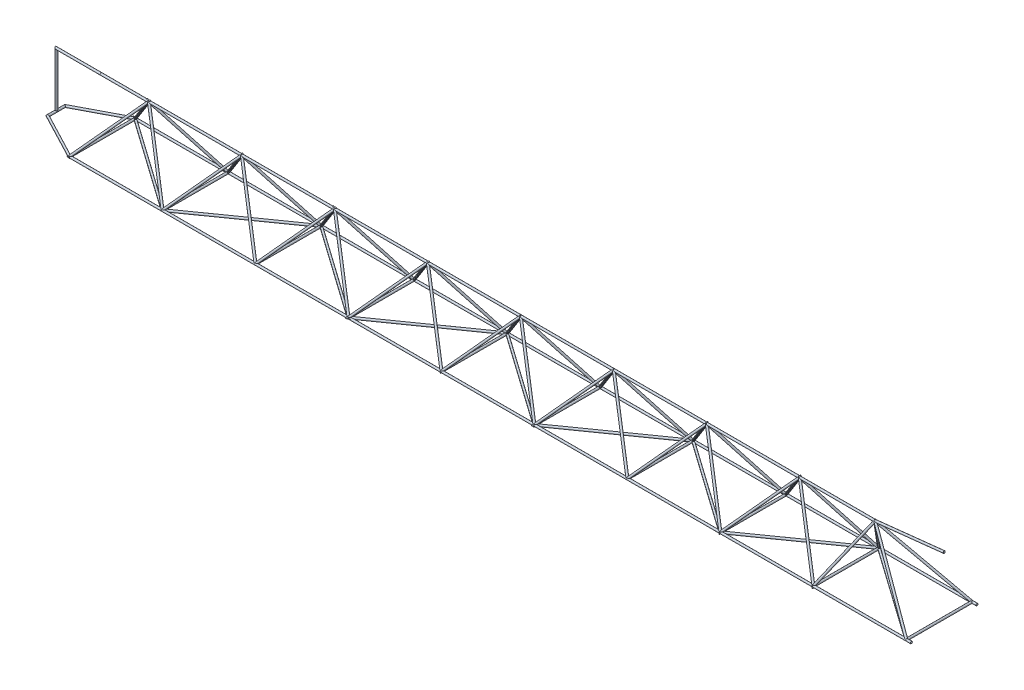
SolidWorks part; units mm, degrees
material "AVG Gam ARM"
ref_plane "Front Plane" through (0, 0, 0) normal (0, 0, 1) x (1, 0, 0)
ref_plane "Top Plane" through (0, 0, 0) normal (0, 1, 0) x (1, 0, 0)
ref_plane "Right Plane" through (0, 0, 0) normal (1, 0, 0) x (0, 0, -1)
sketch3d "3DSketch1"
  line L0 (-4292.6, 0, 0) -> (-3338.6889, 0, 0)
  line L1 (-3338.6889, 0, 0) -> (-2384.7778, 0, 0)
  line L2 (-2384.7778, 0, 0) -> (-1430.8667, 0, 0)
  line L3 (-1430.8667, 0, 0) -> (-476.9556, 0, 0)
  line L4 (-476.9556, 0, 0) -> (476.9556, 0, 0)
  line L5 (476.9556, 0, 0) -> (1430.8667, 0, 0)
  line L6 (1430.8667, 0, 0) -> (2384.7778, 0, 0)
  line L7 (2384.7778, 0, 0) -> (3338.6889, 0, 0)
  line L8 (3338.6889, 0, 0) -> (4292.6, 0, 0)
  line L9 (-4292.6, 0, 0) -> (-4292.6, 0, -673.1)
  line L10 (4292.6, 0, 0) -> (4292.6, 0, -673.1)
  line L11 (-4292.6, 0, -336.55) -> (4292.6, 0, -336.55) construction
  line L12 (-4292.6, 0, -673.1) -> (-3338.6889, 0, -673.1)
  line L13 (-3338.6889, 0, -673.1) -> (-2384.7778, 0, -673.1)
  line L14 (-2384.7778, 0, -673.1) -> (-1430.8667, 0, -673.1)
  line L15 (-1430.8667, 0, -673.1) -> (-476.9556, 0, -673.1)
  line L16 (-476.9556, 0, -673.1) -> (476.9556, 0, -673.1)
  line L17 (476.9556, 0, -673.1) -> (1430.8667, 0, -673.1)
  line L18 (1430.8667, 0, -673.1) -> (2384.7778, 0, -673.1)
  line L19 (2384.7778, 0, -673.1) -> (3338.6889, 0, -673.1)
  line L20 (3338.6889, 0, -673.1) -> (4292.6, 0, -673.1)
  line L21 (4292.6, 0, 0) -> (3338.6889, 0, -673.1)
  line L22 (3338.6889, 0, -673.1) -> (3338.6889, 0, 0)
  line L23 (2384.7778, 0, 0) -> (2384.7778, 0, -673.1)
  line L24 (1430.8667, 0, -673.1) -> (1430.8667, 0, 0)
  line L25 (476.9556, 0, 0) -> (476.9556, 0, -673.1)
  line L26 (-476.9556, 0, 0) -> (-476.9556, 0, -673.1)
  line L27 (-1430.8667, 0, -673.1) -> (-1430.8667, 0, 0)
  line L28 (-2384.7778, 0, 0) -> (-2384.7778, 0, -673.1)
  line L29 (-3338.6889, 0, -673.1) -> (-3338.6889, 0, 0)
  line L30 (3338.6889, 0, -673.1) -> (2384.7778, 0, 0)
  line L31 (2384.7778, 0, 0) -> (1430.8667, 0, -673.1)
  line L32 (1430.8667, 0, -673.1) -> (476.9556, 0, 0)
  line L33 (476.9556, 0, 0) -> (-476.9556, 0, -673.1)
  line L34 (-476.9556, 0, -673.1) -> (-1430.8667, 0, 0)
  line L35 (-1430.8667, 0, 0) -> (-2384.7778, 0, -673.1)
  line L36 (-2384.7778, 0, -673.1) -> (-3338.6889, 0, 0)
  line L37 (-3338.6889, 0, 0) -> (-4292.6, 0, -673.1)
  line L38 (4292.6, 0, -673.1) -> (4343.4, 0, -673.1)
  line L40 (4292.6, 0, 0) -> (4343.4, 0, 0)
  line L42 (4292.6, 0, 0) -> (3635.2852, 558.8, -336.55)
  line L43 (4292.6, 0, -673.1) -> (3635.2852, 558.8, -336.55)
  line L46 (3635.2852, 558.8, -336.55) -> (-4304.2322, 558.8, -336.55)
  line L47 (3338.6889, 0, -673.1) -> (3635.2852, 558.8, -336.55)
  line L48 (3635.2852, 558.8, -336.55) -> (4343.4, 635, -336.55)
  line L49 (3338.6889, 0, 0) -> (3635.2852, 558.8, -336.55)
  line L50 (3338.6889, 0, -673.1) -> (2861.7333, 558.8, -336.55)
  line L51 (2861.7333, 558.8, -336.55) -> (3338.6889, 0, 0)
  line L52 (2384.7778, 0, 0) -> (2861.7333, 558.8, -336.55)
  line L53 (2384.7778, 0, -673.1) -> (2861.7333, 558.8, -336.55)
  line L54 (1430.8667, 0, -673.1) -> (1907.8222, 558.8, -336.55)
  line L55 (1907.8222, 558.8, -336.55) -> (2384.7778, 0, -673.1)
  line L56 (2384.7778, 0, 0) -> (1907.8222, 558.8, -336.55)
  line L57 (1430.8667, 0, 0) -> (1907.8222, 558.8, -336.55)
  line L58 (476.9556, 0, -673.1) -> (953.9111, 558.8, -336.55)
  line L59 (953.9111, 558.8, -336.55) -> (1430.8667, 0, -673.1)
  line L60 (1430.8667, 0, 0) -> (953.9111, 558.8, -336.55)
  line L61 (953.9111, 558.8, -336.55) -> (476.9556, 0, 0)
  line L62 (-476.9556, 0, -673.1) -> (0, 558.8, -336.55)
  line L63 (0, 558.8, -336.55) -> (476.9556, 0, -673.1)
  line L64 (476.9556, 0, 0) -> (0, 558.8, -336.55)
  line L65 (-476.9556, 0, 0) -> (0, 558.8, -336.55)
  line L66 (-476.9556, 0, -673.1) -> (-953.9111, 558.8, -336.55)
  line L67 (-953.9111, 558.8, -336.55) -> (-1430.8667, 0, -673.1)
  line L68 (-1430.8667, 0, 0) -> (-953.9111, 558.8, -336.55)
  line L69 (-476.9556, 0, 0) -> (-953.9111, 558.8, -336.55)
  line L70 (-2384.7778, 0, -673.1) -> (-1907.8222, 558.8, -336.55)
  line L71 (-1907.8222, 558.8, -336.55) -> (-1430.8667, 0, -673.1)
  line L72 (-1430.8667, 0, 0) -> (-1907.8222, 558.8, -336.55)
  line L73 (-1907.8222, 558.8, -336.55) -> (-2384.7778, 0, 0)
  line L74 (-2384.7778, 0, 0) -> (-2861.7333, 558.8, -336.55)
  line L75 (-2861.7333, 558.8, -336.55) -> (-3338.6889, 0, 0)
  line L76 (-3338.6889, 0, -673.1) -> (-2861.7333, 558.8, -336.55)
  line L77 (-2861.7333, 558.8, -336.55) -> (-2384.7778, 0, -673.1)
  line L78 (-4292.6, 0, -673.1) -> (-3815.6444, 558.8, -336.55)
  line L79 (-3815.6444, 558.8, -336.55) -> (-3338.6889, 0, -673.1)
  line L80 (-3338.6889, 0, 0) -> (-3815.6444, 558.8, -336.55)
  line L81 (-3815.6444, 558.8, -336.55) -> (-4292.6, 0, 0)
  line L82 (-4292.6, 0, -673.1) -> (-4765.0246, 0, -425.45)
  line L83 (-4765.0246, 0, -425.45) -> (-4765.0246, 0, -247.65)
  line L84 (-4765.0246, 0, -247.65) -> (-4292.6, 0, 0)
  line L85 (-4765.0246, 0, -336.55) -> (-4765.0246, 558.8, -336.55)
  line L86 (-4304.2322, 558.8, -336.55) -> (-4765.0246, 558.8, -336.55)
  point P10 (0, 0, 0)
  dimension "D1" = 8585.2
  dimension "D2" = 673.1
  dimension "D3" = 50.8
  dimension "D7" = 533.4
  dimension "D5" = 558.8
  dimension "D6" = 7939.5174
  dimension "D8" = 177.8
  dimension "D9" = 558.8
other "Pipe 21.3 X 2.3(1)" corner treatment miter
ref_plane "Plane2" through (3635.2852, 558.8, -336.55) normal (-1, 0, 0) x (0, 0, 1)
sketch "Sketch11" plane through (3635.2852, 558.8, -336.55) normal (-1, 0, 0) x (0, 0, 1)
  circle A0 centre (0, 0) radius 8.35
  circle A1 centre (0, 0) radius 10.65
  point P3 (0, 10.65)
  point P5 (-10.65, 0)
  point P6 (0, -10.65)
  point P7 (10.65, 0)
  point P8 (0, 0)
  dimension "In_dia" = 16.7
  dimension "Out_dia" = 21.3
other "Pipe 21.3 X 2.3(2)" corner treatment miter
ref_plane "Plane3" through (-4292.6, 0, -673.1) normal (-0.8857, 0, 0.4643) x (0.4643, 0, 0.8857)
sketch "Sketch1" plane through (-4292.6, 0, -673.1) normal (-0.8857, 0, 0.4643) x (0.4643, 0, 0.8857)
  circle A0 centre (0, 0) radius 8.35
  circle A1 centre (0, 0) radius 10.65
  point P3 (0, 10.65)
  point P5 (-10.65, 0)
  point P6 (0, -10.65)
  point P7 (10.65, 0)
  point P8 (0, 0)
  dimension "In_dia" = 16.7
  dimension "Out_dia" = 21.3
other "Pipe 21.3 X 2.3(3)" corner treatment miter
ref_plane "Plane4" through (-3338.6889, 0, 0) normal (-0.8171, 0, -0.5765) x (-0.5765, 0, 0.8171)
sketch "Sketch12" plane through (-3338.6889, 0, 0) normal (-0.8171, 0, -0.5765) x (-0.5765, 0, 0.8171)
  circle A0 centre (0, 0) radius 8.35
  circle A1 centre (0, 0) radius 10.65
  point P3 (0, 10.65)
  point P5 (-10.65, 0)
  point P6 (0, -10.65)
  point P7 (10.65, 0)
  point P8 (0, 0)
  dimension "In_dia" = 16.7
  dimension "Out_dia" = 21.3
other "Pipe 21.3 X 2.3(4)" corner treatment miter
ref_plane "Plane5" through (-4292.6, 0, -673.1) normal (0.5902, 0.6915, 0.4165) x (0.7541, -0.2881, -0.5902)
sketch "Sketch13" plane through (-4292.6, 0, -673.1) normal (0.5902, 0.6915, 0.4165) x (0.7541, -0.2881, -0.5902)
  circle A0 centre (0, 0) radius 8.35
  circle A1 centre (0, 0) radius 10.65
  point P3 (0, 10.65)
  point P5 (-10.65, 0)
  point P6 (0, -10.65)
  point P7 (10.65, 0)
  point P8 (0, 0)
  dimension "In_dia" = 16.7
  dimension "Out_dia" = 21.3
other "Pipe 21.3 X 2.3(5)" corner treatment miter
ref_plane "Plane6" through (-3815.6444, 558.8, -336.55) normal (0.5902, -0.6915, -0.4165) x (0.403, 0.6994, -0.5902)
sketch "Sketch14" plane through (-3815.6444, 558.8, -336.55) normal (0.5902, -0.6915, -0.4165) x (0.403, 0.6994, -0.5902)
  circle A0 centre (0, 0) radius 8.35
  circle A1 centre (0, 0) radius 10.65
  point P3 (0, 10.65)
  point P5 (-10.65, 0)
  point P6 (0, -10.65)
  point P7 (10.65, 0)
  point P8 (0, 0)
  dimension "In_dia" = 16.7
  dimension "Out_dia" = 21.3
other "Pipe 21.3 X 2.3(6)" corner treatment miter
ref_plane "Plane7" through (-3338.6889, 0, -673.1) normal (0, 0, 1) x (1, 0, 0)
sketch "Sketch15" plane through (-3338.6889, 0, -673.1) normal (0, 0, 1) x (1, 0, 0)
  circle A0 centre (0, 0) radius 8.35
  circle A1 centre (0, 0) radius 10.65
  point P3 (0, 10.65)
  point P5 (-10.65, 0)
  point P6 (0, -10.65)
  point P7 (10.65, 0)
  point P8 (0, 0)
  dimension "In_dia" = 16.7
  dimension "Out_dia" = 21.3
other "Pipe 21.3 X 2.3(7)" corner treatment miter
ref_plane "Plane8" through (-2384.7778, 0, -673.1) normal (-0.8171, 0, 0.5765) x (0.5765, 0, 0.8171)
sketch "Sketch18" plane through (-2384.7778, 0, -673.1) normal (-0.8171, 0, 0.5765) x (0.5765, 0, 0.8171)
  circle A0 centre (0, 0) radius 8.35
  circle A1 centre (0, 0) radius 10.65
  point P3 (0, 10.65)
  point P5 (-10.65, 0)
  point P6 (0, -10.65)
  point P7 (10.65, 0)
  point P8 (0, 0)
  dimension "In_dia" = 16.7
  dimension "Out_dia" = 21.3
other "Pipe 21.3 X 2.3(8)" corner treatment miter
ref_plane "Plane9" through (-2861.7333, 558.8, -336.55) normal (0.5902, -0.6915, -0.4165) x (0.403, 0.6994, -0.5902)
sketch "Sketch19" plane through (-2861.7333, 558.8, -336.55) normal (0.5902, -0.6915, -0.4165) x (0.403, 0.6994, -0.5902)
  circle A0 centre (0, 0) radius 8.35
  circle A1 centre (0, 0) radius 10.65
  point P3 (0, 10.65)
  point P5 (-10.65, 0)
  point P6 (0, -10.65)
  point P7 (10.65, 0)
  point P8 (0, 0)
  dimension "In_dia" = 16.7
  dimension "Out_dia" = 21.3
other "Pipe 21.3 X 2.3(9)" corner treatment miter
ref_plane "Plane10" through (-1430.8667, 0, 0) normal (-0.5902, 0.6915, -0.4165) x (0.403, 0.6994, 0.5902)
sketch "Sketch110" plane through (-1430.8667, 0, 0) normal (-0.5902, 0.6915, -0.4165) x (0.403, 0.6994, 0.5902)
  circle A0 centre (0, 0) radius 8.35
  circle A1 centre (0, 0) radius 10.65
  point P3 (0, 10.65)
  point P5 (-10.65, 0)
  point P6 (0, -10.65)
  point P7 (10.65, 0)
  point P8 (0, 0)
  dimension "In_dia" = 16.7
  dimension "Out_dia" = 21.3
other "Pipe 21.3 X 2.3(10)" corner treatment miter
ref_plane "Plane11" through (-2384.7778, 0, -673.1) normal (1, 0, 0) x (0, 0, -1)
sketch "Sketch111" plane through (-2384.7778, 0, -673.1) normal (1, 0, 0) x (0, 0, -1)
  circle A0 centre (0, 0) radius 8.35
  circle A1 centre (0, 0) radius 10.65
  point P3 (0, 10.65)
  point P5 (-10.65, 0)
  point P6 (0, -10.65)
  point P7 (10.65, 0)
  point P8 (0, 0)
  dimension "In_dia" = 16.7
  dimension "Out_dia" = 21.3
other "Pipe 21.3 X 2.3(11)" corner treatment miter
ref_plane "Plane12" through (-1430.8667, 0, -673.1) normal (1, 0, 0) x (0, 0, -1)
sketch "Sketch112" plane through (-1430.8667, 0, -673.1) normal (1, 0, 0) x (0, 0, -1)
  circle A0 centre (0, 0) radius 8.35
  circle A1 centre (0, 0) radius 10.65
  point P3 (0, 10.65)
  point P5 (-10.65, 0)
  point P6 (0, -10.65)
  point P7 (10.65, 0)
  point P8 (0, 0)
  dimension "In_dia" = 16.7
  dimension "Out_dia" = 21.3
other "Pipe 21.3 X 2.3(12)" corner treatment miter
ref_plane "Plane13" through (-1430.8667, 0, -673.1) normal (0, 0, 1) x (1, 0, 0)
sketch "Sketch113" plane through (-1430.8667, 0, -673.1) normal (0, 0, 1) x (1, 0, 0)
  circle A0 centre (0, 0) radius 8.35
  circle A1 centre (0, 0) radius 10.65
  point P3 (0, 10.65)
  point P5 (-10.65, 0)
  point P6 (0, -10.65)
  point P7 (10.65, 0)
  point P8 (0, 0)
  dimension "In_dia" = 16.7
  dimension "Out_dia" = 21.3
other "Pipe 21.3 X 2.3(13)" corner treatment miter
ref_plane "Plane14" through (-1430.8667, 0, 0) normal (1, 0, 0) x (0, 0, -1)
sketch "Sketch114" plane through (-1430.8667, 0, 0) normal (1, 0, 0) x (0, 0, -1)
  circle A0 centre (0, 0) radius 8.35
  circle A1 centre (0, 0) radius 10.65
  point P3 (0, 10.65)
  point P5 (-10.65, 0)
  point P6 (0, -10.65)
  point P7 (10.65, 0)
  point P8 (0, 0)
  dimension "In_dia" = 16.7
  dimension "Out_dia" = 21.3
other "Pipe 21.3 X 2.3(14)" corner treatment miter
ref_plane "Plane15" through (-476.9556, 0, -673.1) normal (-0.5902, 0.6915, 0.4165) x (0.7541, 0.2881, 0.5902)
sketch "Sketch115" plane through (-476.9556, 0, -673.1) normal (-0.5902, 0.6915, 0.4165) x (0.7541, 0.2881, 0.5902)
  circle A0 centre (0, 0) radius 8.35
  circle A1 centre (0, 0) radius 10.65
  point P3 (0, 10.65)
  point P5 (-10.65, 0)
  point P6 (0, -10.65)
  point P7 (10.65, 0)
  point P8 (0, 0)
  dimension "In_dia" = 16.7
  dimension "Out_dia" = 21.3
other "Pipe 21.3 X 2.3(15)" corner treatment miter
ref_plane "Plane16" through (4292.6, 0, 0) normal (-0.7098, 0.6034, -0.3634) x (0.2086, 0.6728, 0.7098)
sketch "Sketch116" plane through (4292.6, 0, 0) normal (-0.7098, 0.6034, -0.3634) x (0.2086, 0.6728, 0.7098)
  circle A0 centre (0, 0) radius 8.35
  circle A1 centre (0, 0) radius 10.65
  point P3 (0, 10.65)
  point P5 (-10.65, 0)
  point P6 (0, -10.65)
  point P7 (10.65, 0)
  point P8 (0, 0)
  dimension "In_dia" = 16.7
  dimension "Out_dia" = 21.3
other "Pipe 21.3 X 2.3(16)" corner treatment miter
ref_plane "Plane17" through (476.9556, 0, 0) normal (-0.8171, 0, -0.5765) x (-0.5765, 0, 0.8171)
sketch "Sketch117" plane through (476.9556, 0, 0) normal (-0.8171, 0, -0.5765) x (-0.5765, 0, 0.8171)
  circle A0 centre (0, 0) radius 8.35
  circle A1 centre (0, 0) radius 10.65
  point P3 (0, 10.65)
  point P5 (-10.65, 0)
  point P6 (0, -10.65)
  point P7 (10.65, 0)
  point P8 (0, 0)
  dimension "In_dia" = 16.7
  dimension "Out_dia" = 21.3
other "Pipe 21.3 X 2.3(17)" corner treatment miter
ref_plane "Plane18" through (4292.6, 0, 0) normal (-0.8171, 0, -0.5765) x (-0.5765, 0, 0.8171)
sketch "Sketch118" plane through (4292.6, 0, 0) normal (-0.8171, 0, -0.5765) x (-0.5765, 0, 0.8171)
  circle A0 centre (0, 0) radius 8.35
  circle A1 centre (0, 0) radius 10.65
  point P3 (0, 10.65)
  point P5 (-10.65, 0)
  point P6 (0, -10.65)
  point P7 (10.65, 0)
  point P8 (0, 0)
  dimension "In_dia" = 16.7
  dimension "Out_dia" = 21.3
other "Pipe 21.3 X 2.3(18)" corner treatment miter
ref_plane "Plane19" through (2384.7778, 0, 0) normal (1, 0, 0) x (0, 0, -1)
sketch "Sketch119" plane through (2384.7778, 0, 0) normal (1, 0, 0) x (0, 0, -1)
  circle A0 centre (0, 0) radius 8.35
  circle A1 centre (0, 0) radius 10.65
  point P3 (0, 10.65)
  point P5 (-10.65, 0)
  point P6 (0, -10.65)
  point P7 (10.65, 0)
  point P8 (0, 0)
  dimension "In_dia" = 16.7
  dimension "Out_dia" = 21.3
other "Pipe 21.3 X 2.3(19)" corner treatment miter
ref_plane "Plane20" through (-476.9556, 0, 0) normal (1, 0, 0) x (0, 0, -1)
sketch "Sketch120" plane through (-476.9556, 0, 0) normal (1, 0, 0) x (0, 0, -1)
  circle A0 centre (0, 0) radius 8.35
  circle A1 centre (0, 0) radius 10.65
  point P3 (0, 10.65)
  point P5 (-10.65, 0)
  point P6 (0, -10.65)
  point P7 (10.65, 0)
  point P8 (0, 0)
  dimension "In_dia" = 16.7
  dimension "Out_dia" = 21.3
other "Pipe 21.3 X 2.3(20)" corner treatment miter
ref_plane "Plane21" through (2384.7778, 0, 0) normal (0, 0, -1) x (1, 0, 0)
sketch "Sketch121" plane through (2384.7778, 0, 0) normal (0, 0, -1) x (1, 0, 0)
  circle A0 centre (0, 0) radius 8.35
  circle A1 centre (0, 0) radius 10.65
  point P3 (0, 10.65)
  point P5 (-10.65, 0)
  point P6 (0, -10.65)
  point P7 (10.65, 0)
  point P8 (0, 0)
  dimension "In_dia" = 16.7
  dimension "Out_dia" = 21.3
other "Pipe 21.3 X 2.3(21)" corner treatment miter
ref_plane "Plane22" through (1430.8667, 0, -673.1) normal (0, 0, 1) x (1, 0, 0)
sketch "Sketch122" plane through (1430.8667, 0, -673.1) normal (0, 0, 1) x (1, 0, 0)
  circle A0 centre (0, 0) radius 8.35
  circle A1 centre (0, 0) radius 10.65
  point P3 (0, 10.65)
  point P5 (-10.65, 0)
  point P6 (0, -10.65)
  point P7 (10.65, 0)
  point P8 (0, 0)
  dimension "In_dia" = 16.7
  dimension "Out_dia" = 21.3
other "Pipe 21.3 X 2.3(65)" corner treatment miter
ref_plane "Plane23" through (4292.6, 0, -673.1) normal (1, 0, 0) x (0, 0, -1)
sketch "Sketch124" plane through (4292.6, 0, -673.1) normal (1, 0, 0) x (0, 0, -1)
  circle A0 centre (0, 0) radius 8.35
  circle A1 centre (0, 0) radius 10.65
  point P3 (0, 10.65)
  point P5 (-10.65, 0)
  point P6 (0, -10.65)
  point P7 (10.65, 0)
  point P8 (0, 0)
  dimension "In_dia" = 16.7
  dimension "Out_dia" = 21.3
